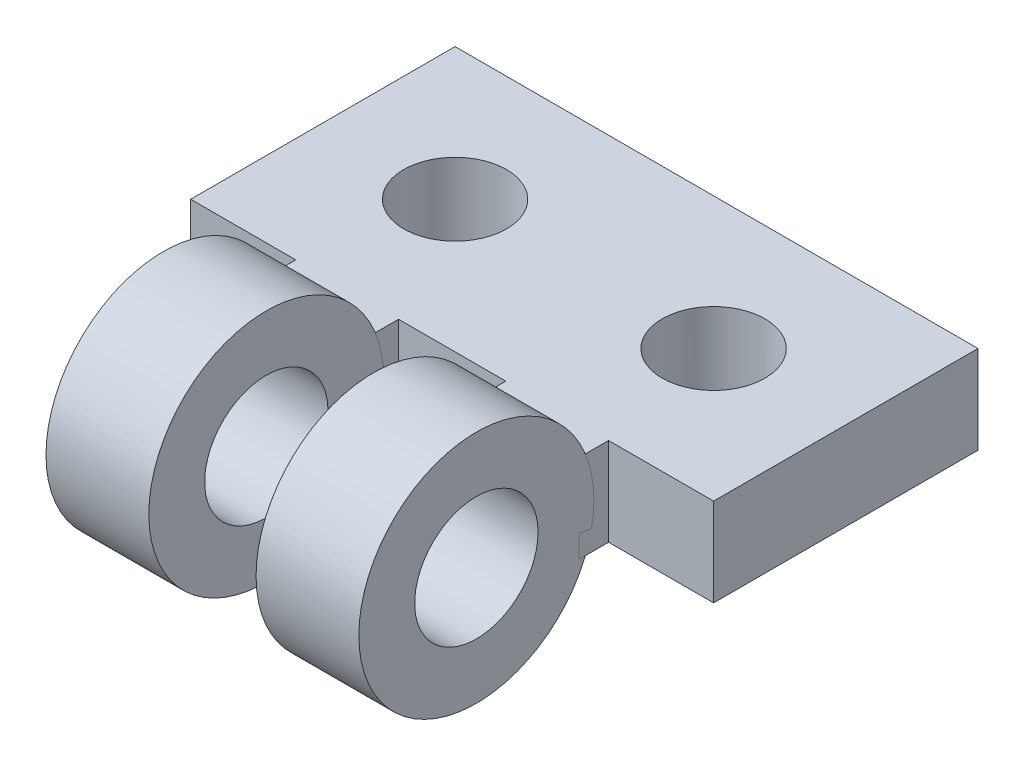
SolidWorks part; units mm, degrees
material "Acrílico (Impacto medio-alto)"
ref_plane "Alzado" through (0, 0, 0) normal (0, 0, 1) x (1, 0, 0)
ref_plane "Planta" through (0, 0, 0) normal (0, 1, 0) x (1, 0, 0)
ref_plane "Vista lateral" through (0, 0, 0) normal (1, 0, 0) x (0, 0, -1)
sketch "Croquis1" plane through (0, 0, 0) normal (1, 0, 0) x (0, -1, 0)
  circle A0 centre (0, 0) radius 4
  circle A1 centre (0, 0) radius 2.1
  dimension "D1" = 4.2
  dimension "D2" = 8
extrude "Saliente-Extruir1" add sketch "Croquis1" along normal blind 3.5
ref_axis "Eje1" through (3.5, 0, 0) along (-1, 0, 0)
pattern_linear "MatrizL3" count 2 spacing 7.15 along (-1, 0, 0) of bodies 101
ref_plane "Plano1" through (0, 0, -3.5) normal (0, 0, 1) x (1, 0, 0)
ref_plane "Plano2" through (-1.825, 0, 0) normal (1, 0, 0) x (0, 0, -1)
sketch "Croquis4" plane through (0, 0, -3.5) normal (0, 0, 1) x (1, 0, 0)
  line L1 (-10.725, 1.5) -> (7.075, 1.5)
  line L2 (-10.725, 1.5) -> (-10.725, -1.5)
  line L3 (-10.725, -1.5) -> (7.075, -1.5)
  line L4 (7.075, 1.5) -> (7.075, -1.5)
  line L9 (-1.825, -4.4) -> (-1.825, 4.4) construction
  point P4 (-10.725, 0)
  point P8 (-1.825, 1.5)
  dimension "D1" = 3
  dimension "D2" = 17.8
extrude "Saliente-Extruir2" add sketch "Croquis4" against normal blind 10 separate body
ref_plane "Plano3" through (-1.825, 0, 0) normal (1, 0, 0) x (0, 0, -1)
sketch "Croquis5" plane through (0, 1.5, 0) normal (0, 1, 0) x (1, 0, 0)
  line L0 (7.075, 13.5) -> (-10.725, 13.5) construction
  line L1 (7.075, 13.5) -> (7.075, 3.5) construction
  line L2 (-1.825, 13.5) -> (-1.825, 12.0443) construction
  circle A0 centre (2.575, 9) radius 1.75
  circle A1 centre (-6.225, 9) radius 1.75
  dimension "D1" = 3.5
  dimension "D2" = 4.5
  dimension "D3" = 4.5
extrude "Cortar-Extruir1" cut sketch "Croquis5" against normal through all
sketch "Croquis6" plane through (3.5, 0, 0) normal (1, 0, 0) x (0, 0, -1)
  line L0 (4.5, 4.7014) -> (4.5, -4.7014)
  line L1 (4.5, 4.7014) -> (-4.4968, 4.7014)
  line L2 (-4.4968, 4.7014) -> (-4.4968, -4.7014)
  line L3 (-4.4968, -4.7014) -> (4.5, -4.7014)
  circle A0 centre (0, 0) radius 4.5 construction
  point P6 (4.5, 0)
  dimension "D1" = 9
extrude "Cortar-Extruir2" cut sketch "Croquis6" along normal through all
sketch "Croquis7" plane through (0, 0, 0) normal (-1, 0, 0) x (0, 0, 1)
  line L0 (-4.5, 4.664) -> (-4.5, -4.664)
  line L1 (-4.5, 4.664) -> (4.5553, 4.664)
  line L2 (4.5553, 4.664) -> (4.5553, -4.664)
  line L3 (4.5553, -4.664) -> (-4.5, -4.664)
  circle A0 centre (0, 0) radius 4.5 construction
  point P6 (-4.5, 0)
  dimension "D1" = 9
extrude "Cortar-Extruir3" cut sketch "Croquis7" along normal up to surface (3.65 mm away) up to face at (-3.65, 0, -4)
ref_plane "Plano4" through (-1.825, 0, 0) normal (1, 0, 0) x (0, 0, -1)
mirror "Simetría1" about plane through (-1.825, 0, 0) normal (1, 0, 0) of "Cortar-Extruir2"
